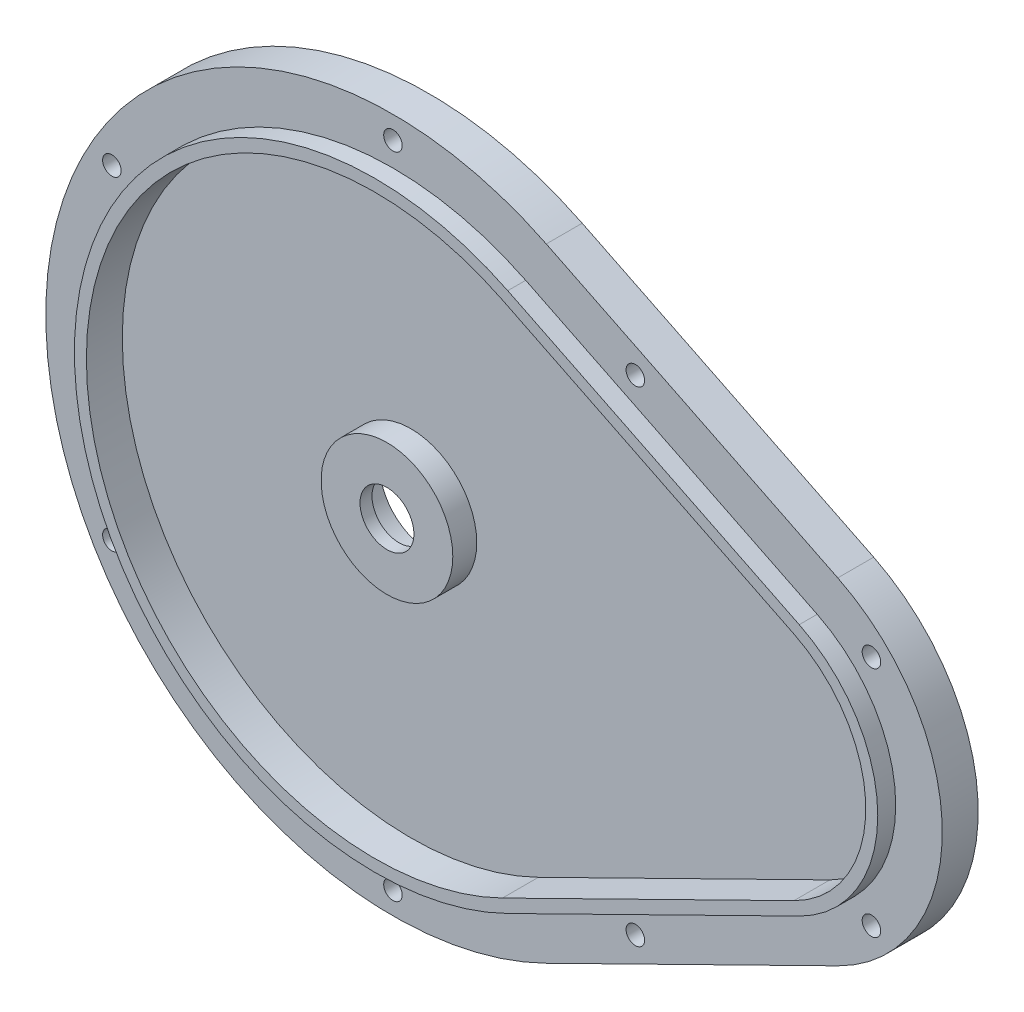
SolidWorks part; units mm, degrees
ref_plane "Front Plane" through (0, 0, 0) normal (0, 0, 1) x (1, 0, 0)
ref_plane "Top Plane" through (0, 0, 0) normal (0, 1, 0) x (1, 0, 0)
ref_plane "Right Plane" through (0, 0, 0) normal (1, 0, 0) x (0, 0, -1)
sketch "Sketch1" plane through (0, 0, 0) normal (0, 0, 1) x (1, 0, 0)
  line L0 (74.3164, 28.0659) -> (25.6181, 52.0393)
  line L1 (0, 0) -> (60.5, 0) construction
  line L5 (74.3164, -28.0659) -> (25.6181, -52.0393)
  circle A1 centre (0, 0) radius 58.0032 construction
  circle A11 centre (60.5, 0) radius 31.2824 construction
  arc A12 (74.3164, 28.0659) -> (74.3164, -28.0659) centre (60.5, 0) cw
  arc A13 (25.6181, 52.0393) -> (25.6181, -52.0393) centre (0, 0) ccw
  point P22 (0, 0)
extrude "Boss-Extrude2" add sketch "Sketch1" along normal blind 6
sketch "Sketch11" plane through (0, 0, 6) normal (0, 0, 1) x (1, 0, 0)
  line L0 (0, 0) -> (60.5, 0) construction
  line L1 (72.6458, 24.6724) -> (23.9475, 48.6458) construction
  line L2 (72.6458, -24.6724) -> (23.9475, -48.6458) construction
  line L3 (0, 0) -> (40.4982, 40.4982) construction
  line L4 (60.5, 0) -> (79.9454, 19.4454) construction
  line L5 (60.5, 0) -> (79.9454, -19.4454) construction
  line L6 (0, 0) -> (40.4982, -40.4982) construction
  circle A25 centre (0, 0) radius 54.2208 construction
  circle A26 centre (60.5, 0) radius 27.5 construction
  circle A27 centre (0, 54.2208) radius 1.55
  circle A28 centre (-46.9566, 27.1104) radius 1.55
  circle A29 centre (-46.9566, -27.1104) radius 1.55
  circle A30 centre (0, -54.2208) radius 1.55
  circle A31 centre (79.9454, 19.4454) radius 1.55
  circle A32 centre (40.4982, 40.4982) radius 1.55
  circle A33 centre (79.9454, -19.4454) radius 1.55
  circle A34 centre (40.4982, -40.4982) radius 1.55
  point P18 (0, 0)
extrude "Cut-Extrude1" cut sketch "Sketch11" against normal up to surface (6 mm away) up to face at (33.4284, 0, 0)
sketch "Sketch12" plane through (0, 0, 6) normal (0, 0, 1) x (1, 0, 0)
  line L0 (22.1809, 45.0571) -> (70.8792, 21.0837)
  line L1 (21.2975, 43.2627) -> (69.9958, 19.2894)
  line L2 (21.2975, -43.2627) -> (69.9958, -19.2894)
  line L3 (22.1809, -45.0571) -> (70.8792, -21.0837)
  circle A0 centre (0, 0) radius 50.2208 construction
  circle A1 centre (60.5, 0) radius 23.5 construction
  arc A2 (69.9958, 19.2894) -> (69.9958, -19.2894) centre (60.5, 0) cw
  arc A3 (70.8792, 21.0837) -> (70.8792, -21.0837) centre (60.5, 0) cw
  circle A4 centre (0, 0) radius 48.2208 construction
  circle A5 centre (60.5, 0) radius 21.5 construction
  arc A6 (21.2975, 43.2627) -> (21.2975, -43.2627) centre (0, 0) ccw
  arc A7 (22.1809, 45.0571) -> (22.1809, -45.0571) centre (0, 0) ccw
extrude "Boss-Extrude3" add sketch "Sketch12" along normal blind 3
sketch "Sketch13" plane through (0, 0, 6) normal (0, 0, 1) x (1, 0, 0)
  line L0 (21.2975, 43.2627) -> (69.9958, 19.2894)
  line L1 (21.2975, -43.2627) -> (69.9958, -19.2894)
  circle A0 centre (0, 0) radius 48.2208 construction
  circle A1 centre (60.5, 0) radius 21.5 construction
  arc A2 (69.9958, 19.2894) -> (69.9958, -19.2894) centre (60.5, 0) cw
  arc A3 (21.2975, 43.2627) -> (21.2975, -43.2627) centre (0, 0) ccw
extrude "Cut-Extrude2" cut sketch "Sketch13" against normal blind 3
sketch "Sketch15" plane through (0, 0, 3) normal (0, 0, 1) x (1, 0, 0)
  circle A0 centre (0, 0) radius 11
extrude "Boss-Extrude4" add sketch "Sketch15" along normal blind 4
sketch "Sketch14" plane through (0, 0, 0) normal (0, 0, -1) x (-1, 0, 0)
  circle A0 centre (0, 0) radius 8.2
extrude "Cut-Extrude3" cut sketch "Sketch14" against normal blind 5
sketch "Sketch16" plane through (0, 0, 0) normal (0, 0, -1) x (-1, 0, 0)
  circle A0 centre (0, 0) radius 4.5
extrude "Cut-Extrude4" cut sketch "Sketch16" against normal up to surface (7 mm away) up to face at (11, 0, 7)
sketch "Sketch17" plane through (0, 0, 0) normal (0, 0, -1) x (-1, 0, 0)
  line L0 (-80.4673, 0) -> (80.4673, 0) construction
  circle A0 centre (46.9566, 27.1104) radius 3.5
  circle A1 centre (0, 54.2208) radius 3.5
  circle A2 centre (-40.4982, 40.4982) radius 3.5
  circle A3 centre (-79.9454, 19.4454) radius 3.5
  circle A4 centre (-79.9454, -19.4454) radius 3.5
  circle A5 centre (-40.4982, -40.4982) radius 3.5
  circle A6 centre (0, -54.2208) radius 3.5
  circle A7 centre (46.9566, -27.1104) radius 3.5
  point P17 (0, 0)
extrude "Cut-Extrude5" cut sketch "Sketch17" against normal blind 3
